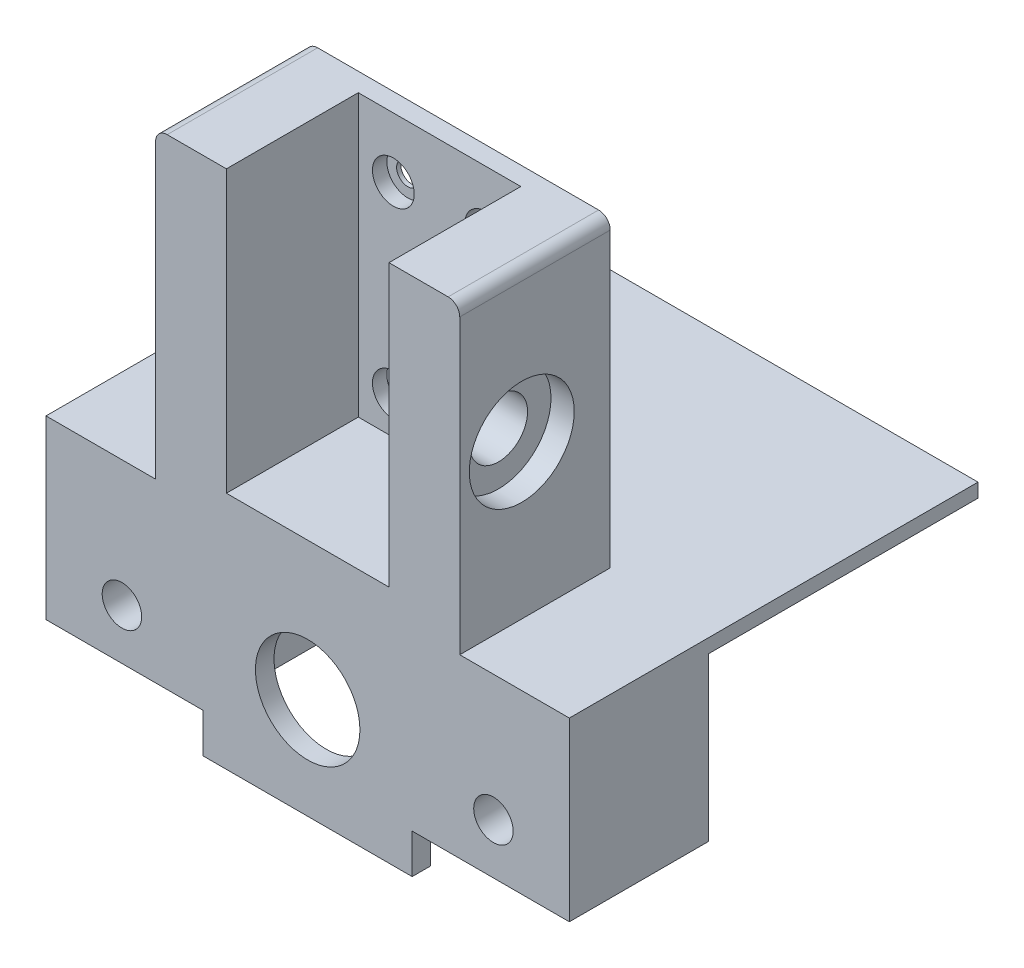
SolidWorks part; units mm, degrees
ref_plane "Front Plane" through (0, 0, 0) normal (0, 0, 1) x (1, 0, 0)
ref_plane "Top Plane" through (0, 0, 0) normal (0, 1, 0) x (1, 0, 0)
ref_plane "Right Plane" through (0, 0, 0) normal (1, 0, 0) x (0, 0, -1)
sketch "Sketch1" plane through (0, 0, 0) normal (0, 0, 1) x (1, 0, 0)
  line L1 (0, 0) -> (-65.5, 0)
  line L2 (0, 0) -> (0, -65.5)
  line L3 (0, -65.5) -> (-65.5, -65.5)
  line L4 (-65.5, 0) -> (-65.5, -65.5)
  line L5 (-17.5, -14.95) -> (-48, -14.95)
  line L6 (-17.5, -14.95) -> (-17.5, -50.55)
  line L7 (-17.5, -50.55) -> (-48, -50.55)
  line L8 (-48, -14.95) -> (-48, -50.55)
  point P10 (-32.75, -14.95)
  point P11 (-48, -32.75)
  point P12 (-65.5, -32.75)
  point P13 (-32.75, 0)
  dimension "D1" = 65.5
  dimension "D2" = 35.6
  dimension "D3" = 30.5
extrude "Boss-Extrude1" add sketch "Sketch1" along normal blind 28.4 and the other way blind 4
sketch "Sketch5" plane through (0, 0, 0) normal (1, 0, 0) x (0, 0, -1)
  line L2 (4, -65.5) -> (4, 0) construction
  line L4 (4, 0) -> (-28.4, 0) construction
  circle A1 centre (-15.05, -32.45) radius 11.3
  dimension "D1" = 11.3
  dimension "D2" = 19.05
  dimension "D3" = 32.45
extrude "Cut-Extrude1" cut sketch "Sketch5" against normal blind 5
sketch "Sketch8" plane through (0, 0, -4) normal (0, 0, -1) x (-1, 0, 0)
  line L4 (17.5, -14.95) -> (17.5, -50.55)
  line L5 (48, -14.95) -> (17.5, -14.95)
  line L6 (48, -50.55) -> (48, -14.95)
  line L7 (17.5, -50.55) -> (48, -50.55)
  line L8 (17.5, -14.95) -> (17.5, -50.55)
  line L9 (48, -14.95) -> (17.5, -14.95)
  line L10 (48, -50.55) -> (48, -14.95)
  line L11 (17.5, -50.55) -> (48, -50.55)
  dimension "D2" = 30.5
  dimension "D3" = 35.6
  dimension "D1" = 0
extrude "Boss-Extrude2" add sketch "Sketch8" against normal blind 4
sketch "Sketch9" plane through (0, 0, -4) normal (0, 0, 1) x (1, 0, 0)
  line L0 (0, 0) -> (-65.5, 0) construction
  line L1 (0, 0) -> (0, -65.5) construction
  line L2 (0, -65.5) -> (-65.5, -65.5) construction
  line L3 (-32.75, -65.5) -> (-32.75, 0) construction
  line L4 (0, -32.75) -> (-65.5, -32.75) construction
  line L5 (-65.5, 0) -> (-65.5, -65.5) construction
  line L6 (-32.75, -65.5) -> (-32.75, -53.5) construction
  line L7 (-65.5, -65.5) -> (0, 0) construction
  circle A0 centre (-12.75, -12.9) radius 4.9
  circle A1 centre (-52.75, -12.9) radius 4.9
  circle A2 centre (-52.75, -52.6) radius 4.9
  circle A3 centre (-12.75, -52.6) radius 4.9
  point P20 (-32.75, -12)
  point P26 (-12, -32.75)
  point P27 (-53.5, -32.75)
  dimension "D3" = 9.8
  dimension "D1" = 12.9
  dimension "D2" = 12.75
  dimension "D4" = 12
extrude "Cut-Extrude5" cut sketch "Sketch9" along normal blind 2.2
fillet "Fillet1" radius 2.5 2 edges at (0, 0, 12.2) (-65.5, 0, 12.2)
sketch "Sketch10" plane through (0, 0, 0) normal (0, 0, 1) x (1, 0, 0)
  line L0 (0, -52.6) -> (-22.8, -52.6) construction
  line L1 (0, 0) -> (0, -65.5) construction
  line L2 (-22.8, -52.6) -> (-22.8, -65.5) construction
  line L3 (0, -65.5) -> (-65.5, -65.5) construction
  line L5 (-32.75, -65.5) -> (-32.75, 0) construction
  line L6 (0, -32.75) -> (-65.5, -32.75) construction
  line L7 (-32.75, -65.5) -> (-32.75, 0) construction
  line L8 (0, -32.75) -> (-65.5, -32.75) construction
  circle A0 centre (-22.8, -12.9) radius 5
  circle A1 centre (-42.7, -12.9) radius 5
  circle A2 centre (-22.8, -52.6) radius 5
  circle A3 centre (-42.7, -52.6) radius 5
  point P7 (-22.8, -12.9)
  point P8 (-42.7, -12.9)
  point P13 (-42.7, -52.6)
  dimension "D3" = 10
  dimension "D1" = 22.8
  dimension "D2" = 12.9
extrude "Cut-Extrude7" cut sketch "Sketch10" along normal up to next
sketch "Sketch20" plane through (0, 0, 0) normal (0, 0, 1) x (1, 0, 0)
  line L0 (-32.75, 0) -> (-32.75, -65.5) construction
  line L1 (-32.75, -65.5) -> (-32.75, 0) construction
  line L2 (-65.5, -32.75) -> (0, -32.75) construction
  line L3 (0, -32.75) -> (-65.5, -32.75) construction
  line L4 (-62.12, -65.5) -> (-3.38, -65.5) construction
  line L5 (0, -65.5) -> (-65.5, -65.5) construction
  line L6 (0, 0) -> (-65.5, 0) construction
  line L7 (0, 0) -> (0, -65.5) construction
  line L8 (-65.5, 0) -> (-65.5, -65.5) construction
  arc A0 (-38.1396, -14.95) -> (-47.2604, -14.95) centre (-42.7, -12.9) ccw construction
  point P0 (-42.7, -12.9)
  point P13 (-22.8, -12.9)
  point P15 (-22.8, -52.6)
  point P16 (-42.7, -52.6)
hole_wizard "CBORE for M4 Pan Head Machine Screw1" positions "3DSketch5" profile "Sketch22" counterbore size "M4" standard "ANSI Metric"
sketch3d "3DSketch5"
  point P0 (-42.7, -12.9, 0)
  point P3 (-22.8, -12.9, 0)
  point P6 (-42.7, -52.6, 0)
  point P9 (-22.8, -52.6, 0)
sketch "Sketch22" plane through (-42.7, -12.9, 0) normal (1, 0, 0) x (0, -1, 0)
  line L0 (0, 0) -> (0, 9.4421)
  line L1 (0, 9.4421) -> (2.4, 8)
  line L2 (2.4, 8) -> (2.4, 3.1)
  line L3 (2.4, 3.1) -> (4.5, 3.1)
  line L4 (4.5, 3.1) -> (4.5, 0)
  line L5 (4.5, 0) -> (0, 0)
  line L10 (0, 9.4421) -> (-2.4, 8) construction
  line L11 (0, -6.35) -> (0, 107.95) construction
  dimension "Hole Dia." = 4.8
  dimension "Hole Depth" = 8
  dimension "C'Bore Dia." = 9
  dimension "C'Bore Depth" = 3.1
  dimension "Drill Angle" = 118
sketch "Sketch23" plane through (0, -65.5, 0) normal (0, -1, 0) x (1, 0, 0)
  line L1 (23.6, 28.4) -> (-89.1, 28.4)
  line L2 (23.6, 28.4) -> (23.6, -59.6)
  line L3 (23.6, -59.6) -> (-89.1, -59.6)
  line L4 (-89.1, 28.4) -> (-89.1, -59.6)
  line L9 (-65.5, 28.4) -> (0, 28.4) construction
  point P4 (-32.75, -59.6)
  dimension "D1" = 88
  dimension "D2" = 112.7
extrude "Boss-Extrude3" add sketch "Sketch23" along normal blind 3
sketch "Sketch24" plane through (0, -68.5, 0) normal (0, -1, 0) x (-1, 0, 0)
  line L0 (-23.6, -28.4) -> (89.1, -28.4) construction
  line L1 (55.25, -28.4) -> (10.25, -28.4)
  line L2 (55.25, -28.4) -> (55.25, -24.4)
  line L3 (55.25, -24.4) -> (10.25, -24.4)
  line L4 (10.25, -28.4) -> (10.25, -24.4)
  point P6 (32.75, -28.4)
  dimension "D1" = 4
  dimension "D2" = 45
extrude "Boss-Extrude4" add sketch "Sketch24" along normal blind 43.5
sketch "Sketch25" plane through (0, 0, 28.4) normal (0, 0, 1) x (1, 0, 0)
  line L1 (-55.25, -68.5) -> (-89.1, -68.5) construction
  line L2 (-32.75, -112) -> (-32.75, 0) construction
  line L3 (-10.25, -112) -> (-55.25, -112) construction
  line L4 (-2.5, 0) -> (-63, 0) construction
  point P0 (-48.25, -74.5)
  point P1 (0, 0)
  point P5 (-48.25, -105.5)
  dimension "D1" = 15.5
  dimension "D2" = 6
  dimension "D3" = 31
sketch "Sketch28" plane through (0, 0, 28.4) normal (0, 0, 1) x (1, 0, 0)
  line L0 (-10.25, -112) -> (-55.25, -68.5) construction
  circle A0 centre (-32.75, -90.25) radius 22.0978
  circle A1 centre (-32.75, -90.25) radius 11.25
  dimension "D1" = 22.5
ref_plane "Plane1" through (-32.75, 0, 0) normal (1, 0, 0) x (0, 0, -1)
extrude "Cut-Extrude8" cut sketch "Sketch28" against normal up to next contours A1
sketch "Sketch29" plane through (0, 0, 28.4) normal (0, 0, 1) x (1, 0, 0)
  line L0 (-32.75, -89.65) -> (-55.25, -89.65) construction
  line L1 (-55.25, -112) -> (-55.25, -68.5) construction
sketch "Sketch30" plane through (0, -68.5, 0) normal (0, -1, 0) x (-1, 0, 0)
  line L1 (55.25, -28.4) -> (89.1, -28.4)
  line L2 (55.25, -28.4) -> (55.25, 1.6)
  line L3 (55.25, 1.6) -> (89.1, 1.6)
  line L4 (89.1, -28.4) -> (89.1, 1.6)
  line L5 (89.1, -28.4) -> (89.1, 59.6) construction
  dimension "D1" = 30
extrude "Boss-Extrude5" add sketch "Sketch30" along normal blind 35
sketch "Sketch31" plane through (0, 0, 28.4) normal (0, 0, 1) x (1, 0, 0)
  line L0 (-72.75, -92.65) -> (-72.75, -103.5) construction
  line L1 (-55.25, -103.5) -> (-89.1, -103.5) construction
  circle A0 centre (-72.75, -92.65) radius 4.25
  dimension "D3" = 8.5
  dimension "D1" = 3
  dimension "D2" = 40
sketch "Sketch33" plane through (0, -103.5, 0) normal (0, -1, 0) x (-1, 0, 0)
  line L0 (72.75, -28.4) -> (72.75, 1.6) construction
  line L1 (89.1, 1.6) -> (55.25, 1.6) construction
  point P5 (72.75, -13.4)
  point P6 (72.75, -21.4)
  point P7 (72.75, -5.4)
  dimension "D1" = 8
  dimension "D2" = 8
extrude "Cut-Extrude10" cut sketch "Sketch31" against normal up to next
hole_wizard "CBORE for M3 Pan Head Machine Screw2" positions "Sketch34" profile "Sketch35" counterbore size "M3" standard "ANSI Metric" end condition up to next
sketch "Sketch34" plane through (0, -103.5, 0) normal (0, -1, 0) x (-1, 0, 0)
  point P0 (72.75, -13.4)
sketch "Sketch35" plane through (-72.75, -103.5, 13.4) normal (1, 0, 0) x (0, 0, -1)
  line L0 (0, 0) -> (0, 6.6)
  line L1 (0, 6.6) -> (1.6, 6.6)
  line L3 (1.6, 6.6) -> (1.6, 2.4)
  line L4 (1.6, 2.4) -> (3.5, 2.4)
  line L5 (3.5, 2.4) -> (3.5, 0)
  line L7 (3.5, 0) -> (0, 0)
  line L11 (0, -6.35) -> (0, 107.95) construction
  dimension "Thru Hole Dia." = 3.2
  dimension "Thru Hole Depth" = 6.6
  dimension "C'Bore Dia." = 7
  dimension "C'Bore Depth" = 2.4
mirror "Mirror2" about plane through (-32.75, 0, 0) normal (1, 0, 0) of "Cut-Extrude10", "CBORE for M3 Pan Head Machine Screw2", "Boss-Extrude5"
sketch "Sketch36" plane through (-5, 0, 0) normal (1, 0, 0) x (0, 0, -1)
  circle A0 centre (-15.05, -32.45) radius 6.25
  circle A1 centre (-15.05, -32.45) radius 11.3 construction
  dimension "D1" = 12.5
extrude "Cut-Extrude11" cut sketch "Sketch36" against normal up to next
sketch "Sketch37" plane through (0, 0, 28.4) normal (0, 0, 1) x (1, 0, 0)
  line L0 (-2.5, 0) -> (-63, 0) construction
  line L1 (-50.25, -60.5) -> (-15.25, -60.5)
  line L2 (-50.25, -60.5) -> (-50.25, 0)
  line L3 (-50.25, 0) -> (-15.25, 0)
  line L4 (-15.25, -60.5) -> (-15.25, 0)
  line L5 (0, -65.5) -> (-65.5, -65.5) construction
  point P12 (-32.75, 0)
  dimension "D1" = 5
  dimension "D2" = 35
extrude "Cut-Extrude12" cut sketch "Sketch37" against normal blind 28.4
